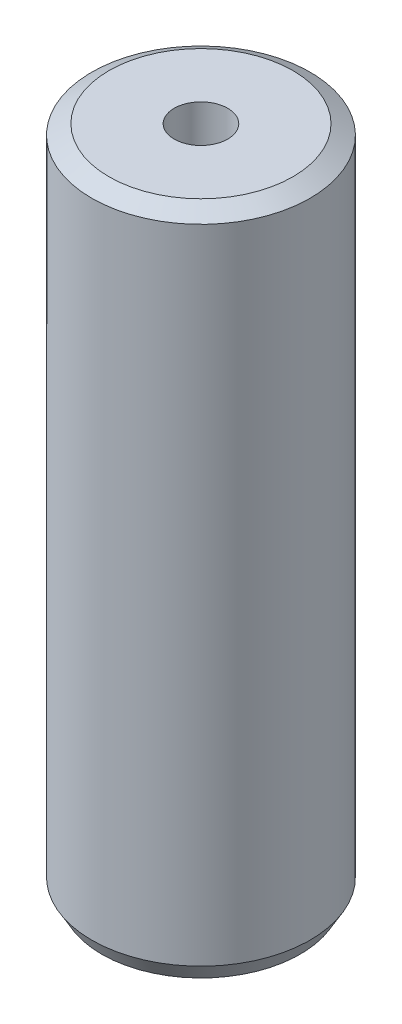
SolidWorks part; units mm, degrees
ref_plane "Front Plane" through (0, 0, 0) normal (0, 0, 1) x (1, 0, 0)
ref_plane "Top Plane" through (0, 0, 0) normal (0, 1, 0) x (1, 0, 0)
ref_plane "Right Plane" through (0, 0, 0) normal (1, 0, 0) x (0, 0, -1)
sketch "Sketch1" plane through (0, 0, 0) normal (0, 1, 0) x (1, 0, 0)
  circle A0 centre (0, 0) radius 10
  dimension "SHAFT_OD" = 20
extrude "Boss-Extrude1" add sketch "Sketch1" along normal blind 61.3128
sketch "Sketch2" plane through (0, 0, 0) normal (0, 1, 0) x (1, 0, 0)
  circle A0 centre (0, 0) radius 2.4495
  dimension "BORE_D" = 4.8991
extrude "Cut-Extrude1" cut sketch "Sketch2" along normal through all
chamfer "Chamfer1" distance 0.9111 angle 60 2 edges at (0, 61.3128, 10) (0, 0, 10) first distance on face at (0, 61.3128, 10) first distance on face at (0, 0, 2.4495)
